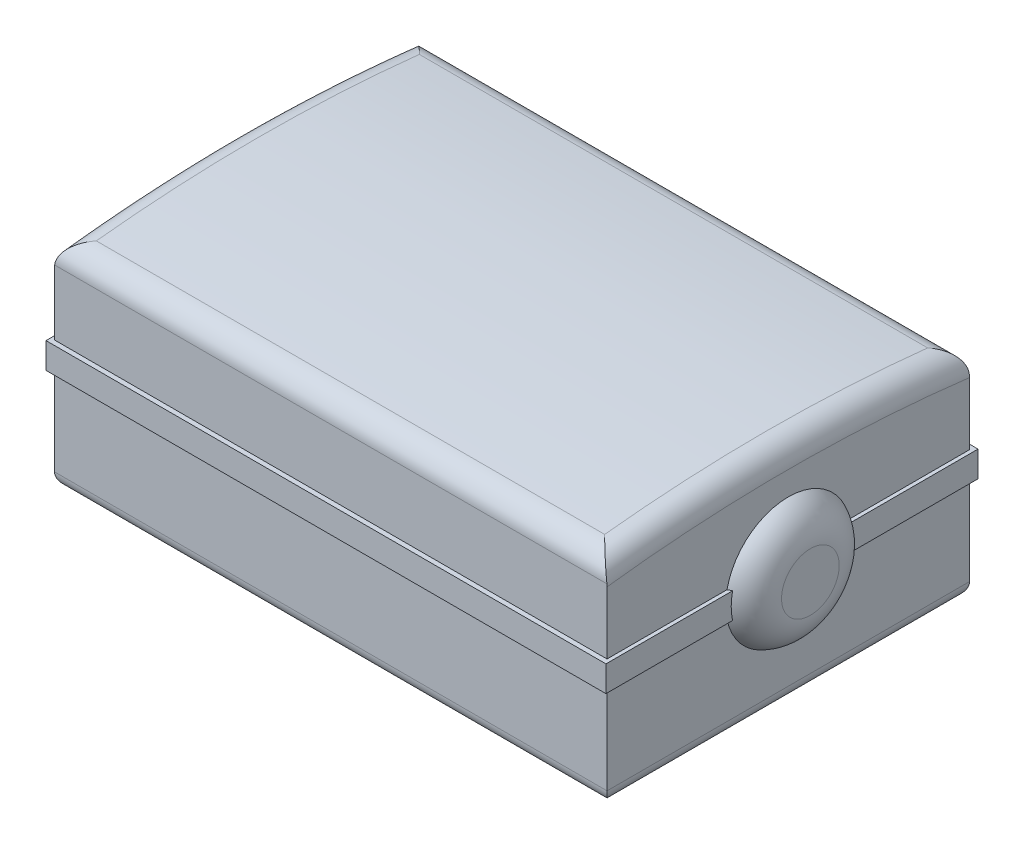
SolidWorks part; units mm, degrees
ref_plane "前视基准面" through (0, 0, 0) normal (0, 0, 1) x (1, 0, 0)
ref_plane "上视基准面" through (0, 0, 0) normal (0, 1, 0) x (1, 0, 0)
ref_plane "右视基准面" through (0, 0, 0) normal (1, 0, 0) x (0, 0, -1)
sketch "草图1" plane through (0, 0, 0) normal (1, 0, 0) x (0, 0, -1)
  line L0 (0, 54.7418) -> (0, -41.7698) construction
  line L1 (-24.6, 0) -> (24.6, 0)
  line L2 (24.6, 0) -> (24.6, 14)
  line L3 (24.6, 14) -> (25.25, 14)
  line L4 (25.25, 14) -> (25.25, 17.5)
  line L5 (25.25, 17.5) -> (24.6, 17.5)
  line L6 (24.6, 17.5) -> (24.6, 29)
  line L7 (-16.7016, 30.5) -> (32.2933, 30.5) construction
  line L8 (-24.6, 17.5) -> (-24.6, 29)
  line L9 (-25.25, 17.5) -> (-24.6, 17.5)
  line L10 (-25.25, 14) -> (-25.25, 17.5)
  line L11 (-24.6, 14) -> (-25.25, 14)
  line L12 (-24.6, 0) -> (-24.6, 14)
  arc A0 (24.6, 29) -> (-24.6, 29) centre (0, -174.1806) ccw
  point P19 (0, 0)
  dimension "D1" = 24.6
  dimension "D2" = 25.25
  dimension "D3" = 14
  dimension "D4" = 3.5
  dimension "D5" = 30.5
  dimension "D6" = 29
extrude "凸台-拉伸1" add sketch "草图1" along normal blind 37.5 and the other way blind 37.5
sketch "草图2" plane through (-37.5, 0, 0) normal (-1, 0, 0) x (0, 0, 1)
  line L0 (-30.1987, 15.75) -> (29.9736, 15.75) construction
  line L1 (0, -5.4658) -> (0, 38.3504) construction
  line L2 (-25.25, 17.5) -> (-24.6, 17.5) construction
  line L3 (-24.6, 14) -> (-25.25, 14) construction
  circle A0 centre (0, 15.75) radius 8.5
  dimension "D1" = 17
extrude "凸台-拉伸3" add sketch "草图2" along normal blind 3
mirror "镜向1" about plane through (0, 0, 0) normal (1, 0, 0) of "凸台-拉伸3"
fillet "圆角1" radius 5 2 edges at (40.5, 15.75, 8.5) (-40.5, 15.75, 8.5)
sketch "草图3" plane through (37.5, 0, 0) normal (1, 0, 0) x (0, 0, -1)
  line L0 (25.25, 14) -> (25.25, 17.5) construction
  line L1 (-25.25, 17.5) -> (25.25, 17.5)
  line L2 (-25.25, 17.5) -> (-25.25, 14)
  line L3 (-25.25, 14) -> (25.25, 14)
  line L4 (25.25, 17.5) -> (25.25, 14)
  line L5 (24.6, 14) -> (25.25, 14) construction
extrude "凸台-拉伸4" add sketch "草图3" along normal blind 0.5
mirror "镜向2" about plane through (0, 0, 0) normal (1, 0, 0) of "凸台-拉伸4"
fillet "圆角2" radius 3 4 edges at (-37.5, 30.4838, 0) (0, 29, -24.6) (0, 29, 24.6) (37.5, 30.4838, 0)
fillet "圆角3" radius 2 4 edges at (0, 0, -24.6) (-37.5, 0, 0) (37.5, 0, 0) (0, 0, 24.6)
